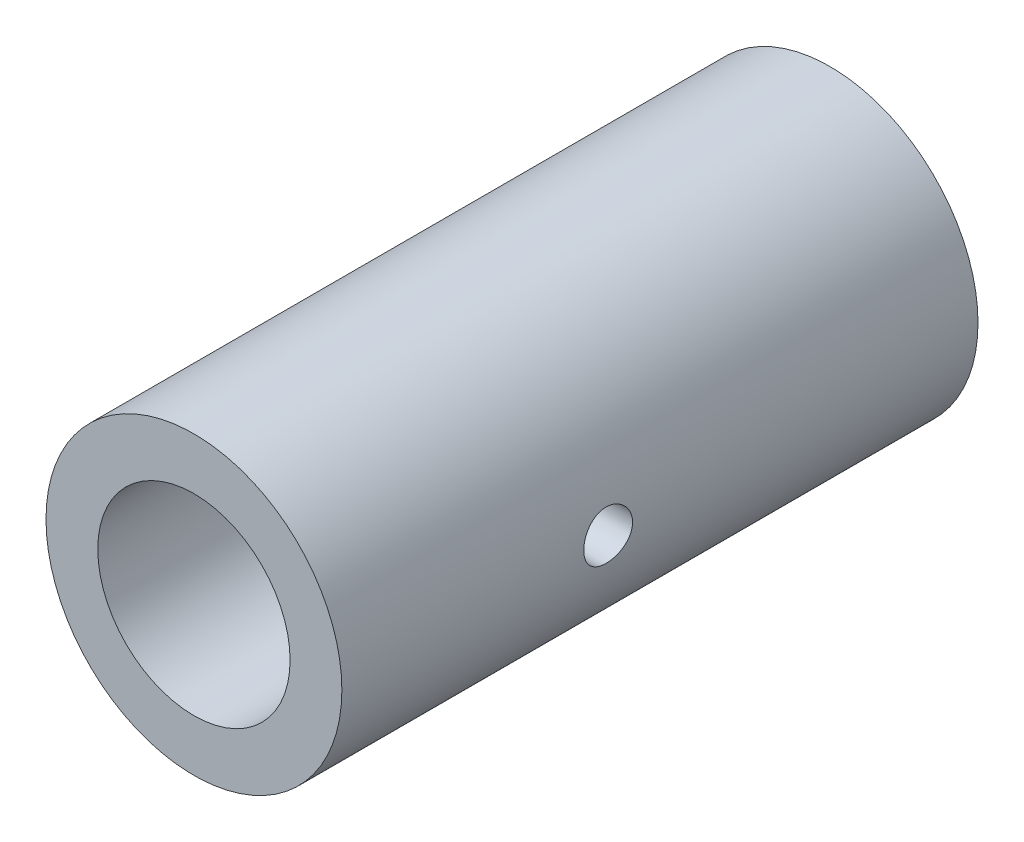
SolidWorks part; units mm, degrees
material "3.1355 (EN-AW 2024)"
ref_plane "Front" through (0, 0, 0) normal (0, 0, 1) x (1, 0, 0)
ref_plane "Top" through (0, 0, 0) normal (0, 1, 0) x (1, 0, 0)
ref_plane "Right" through (0, 0, 0) normal (1, 0, 0) x (0, 0, -1)
sketch "Эскиз1" plane through (0, 0, 0) normal (0, 0, 1) x (1, 0, 0)
  circle A0 centre (0, 0) radius 10
  dimension "D1" = 20
extrude "Бобышка-Вытянуть1" add sketch "Эскиз1" along normal blind 43
sketch "Эскиз2" plane through (0, 0, 43) normal (0, 0, 1) x (1, 0, 0)
  circle A0 centre (0, 0) radius 6.5
  dimension "D1" = 13
extrude "Вырез-Вытянуть1" cut sketch "Эскиз2" against normal blind 27
sketch "Эскиз3" plane through (0, 0, 0) normal (0, 1, 0) x (1, 0, 0)
  line L0 (-10, -43) -> (-10, -25) construction
  dimension "D1" = 18
ref_plane "Плоскость1" through (-10, 0, 0) normal (1, 0, 0) x (0, 0, -1)
hole_wizard "Отверстие обработанное метчиком M4x0.71" positions "Эскиз5" profile "Эскиз4" tap size "M4x0.7" standard "Ansi Metric" end condition through all
sketch "Эскиз5" plane through (-10, 0, 0) normal (1, 0, 0) x (0, 0, -1)
  line L0 (-43, 0) -> (-25, 0) construction
  point P0 (-25, 0)
sketch "Эскиз4" plane through (-10, 0, 25) normal (0, 1, 0) x (0, 0, 1)
  line L0 (0, 0) -> (0, 20)
  line L1 (0, 20) -> (1.65, 20)
  line L2 (1.65, 20) -> (1.65, 0)
  line L5 (1.65, 0) -> (0, 0)
  line L11 (0, -6.35) -> (0, 107.95) construction
  dimension "Диаметр проходного сверла" = 3.3
  dimension "Глубина проходного сверла" = 20
cosmetic thread "Отверстие резьбы6" parameters "D2"=4
sketch "Эскиз7" plane through (0, 0, 0) normal (0, 0, -1) x (-1, 0, 0)
  line L0 (-6, 0) -> (0, 0) construction
  line L1 (0, 0) -> (-4.2426, 4.2426) construction
  line L2 (0, 0) -> (4.2426, 4.2426) construction
  line L3 (0, 0) -> (4.2426, -4.2426) construction
  line L4 (0, 0) -> (-4.2426, -4.2426) construction
  circle A0 centre (0, 0) radius 6 construction
  point P11 (0, 0)
  dimension "D1" = 12
  dimension "D2" = 45
  dimension "D3" = 4
hole_wizard "Отверстие обработанное метчиком M3x0.51" positions "Эскиз9" profile "Эскиз8" tap size "M3x0.5" standard "Ansi Metric"
sketch "Эскиз9" plane through (0, 0, 0) normal (0, 0, -1) x (-1, 0, 0)
  point P0 (-4.2426, 4.2426)
  point P3 (4.2426, 4.2426)
  point P6 (4.2426, -4.2426)
  point P9 (-4.2426, -4.2426)
cosmetic thread "Отверстие резьбы2" parameters "D1"=6, "D2"=3
cosmetic thread "Отверстие резьбы3" parameters "D1"=6, "D2"=3
cosmetic thread "Отверстие резьбы4" parameters "D1"=6, "D2"=3
cosmetic thread "Отверстие резьбы5" parameters "D1"=6, "D2"=3
sketch "Эскиз8" plane through (4.2426, 4.2426, 0) normal (1, 0, 0) x (0, 1, 0)
  line L0 (0, 0) -> (0, 9.2511)
  line L1 (0, 9.2511) -> (1.25, 8.5)
  line L2 (1.25, 8.5) -> (1.25, 0)
  line L5 (1.25, 0) -> (0, 0)
  line L10 (0, 9.2511) -> (-1.25, 8.5) construction
  line L11 (0, -6.35) -> (0, 107.95) construction
  dimension "Диаметр сверла" = 2.5
  dimension "Глубина сверла" = 8.5
  dimension "Угол заточки сверла" = 118
